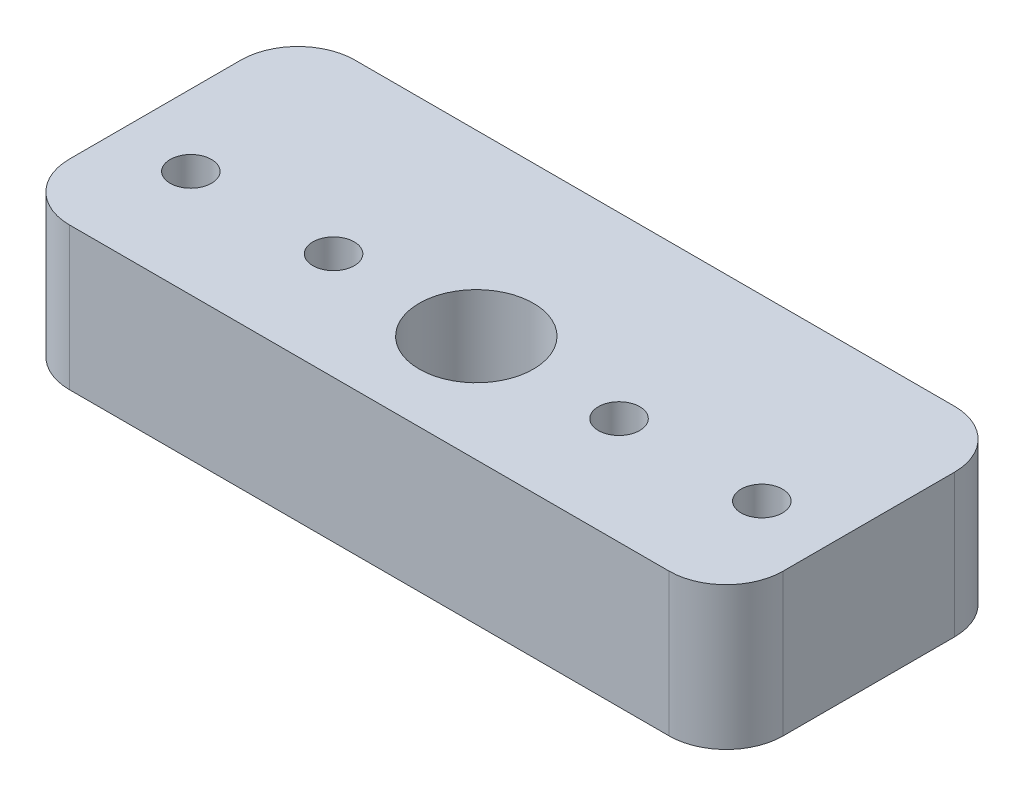
SolidWorks part; units mm, degrees
ref_plane "Front Plane" through (0, 0, 0) normal (0, 0, 1) x (1, 0, 0)
ref_plane "Top Plane" through (0, 0, 0) normal (0, 1, 0) x (1, 0, 0)
ref_plane "Right Plane" through (0, 0, 0) normal (1, 0, 0) x (0, 0, -1)
sketch "Sketch1" plane through (0, 0, 0) normal (0, 1, 0) x (1, 0, 0)
  line L0 (-25, -2.5) -> (25, -2.5) construction
  line L1 (-21, 10) -> (21, 10)
  line L2 (-25, 6) -> (-25, -6)
  line L3 (-21, -10) -> (21, -10)
  line L4 (25, 6) -> (25, -6)
  line L5 (-25, 10) -> (25, -10) construction
  line L6 (-25, -10) -> (25, 10) construction
  line L7 (0, -10) -> (0, 10) construction
  line L8 (25, 10) -> (-25, -10) construction
  arc A0 (-25, -6) -> (-21, -10) centre (-21, -6) ccw
  arc A1 (21, -10) -> (25, -6) centre (21, -6) ccw
  arc A2 (21, 10) -> (25, 6) centre (21, 6) cw
  arc A3 (-21, 10) -> (-25, 6) centre (-21, 6) ccw
  circle A4 centre (0, -2.5) radius 4
  circle A5 centre (10, -2.5) radius 1.45
  circle A6 centre (20, -2.5) radius 1.45
  circle A7 centre (-20, -2.5) radius 1.45
  circle A8 centre (-10, -2.5) radius 1.45
  point P0 (0, 0)
  dimension "D3" = 4
  dimension "D4" = 8
  dimension "D5" = 2.9
  dimension "D6" = 2.9
  dimension "D1" = 20
  dimension "D7" = 7.5
  dimension "D8" = 10
  dimension "D9" = 40
  dimension "D2" = 5
extrude "Boss-Extrude1" add sketch "Sketch1" along normal blind 10
equation "\"Y-ROD-SPACING\"=75"
equation "\"Y-BED-OFFSET\"=2"
equation "\"Y-BED-ROD-INSET\"=3.5"
equation "\"T-SLOT-NUT-FILLET-RADIUS\"=0.5"
equation "\"T-SLOT-SCREW-SHAFT-RADIUS\"=1.55"
equation "\"T-SLOT-SCREW-SHAFT-CUTOUT-LENGTH\"=11.0"
equation "\"T-SLOT-NUT-DEPTH\"=3.5"
equation "\"T-SLOT-NUT-WIDTH\"=2.85"
equation "\"T-SLOT-NUT-END-DISTANCE\"=8"
equation "\"ACRYLIC-TAB-CUTOUT-SIZE\"=\"ACRYLIC-THICKNESS\"+\"ACRYLIC-TAB-TOLERANCE\"*2"
equation "\"ACRYLIC-M3-HOLE\"=2.9"
equation "\"SMOOTHROD-CAP-SCREW-DISTANCE\"=20"
equation "\"D5@Sketch1\"=\"ACRYLIC-M3-HOLE\""
equation "\"D6@Sketch1\"=\"ACRYLIC-M3-HOLE\""
equation "\"D8@Sketch1\"=\"SMOOTHROD-CAP-SCREW-DISTANCE\"/2"
equation "\"ACRYLIC-TAB-WIDTH\"=\"ACRYLIC-THICKNESS\""
equation "\"FRAME-WIDTH-INNER\"=370"
equation "\"NEMA17-HOLE-SPACING\"=31"
equation "\"NEMA17-CENTRAL-CUTOUT\"=22.5"
equation "\"Z-BRACKET-REACH\"=55"
equation "\"TOP-BRACKET-SPACING\"=40"
equation "\"D9@Sketch1\"=\"TOP-BRACKET-SPACING\""
equation "\"D2@Sketch1\"=\"ACRYLIC-TAB-WIDTH\"/2"
equation "\"X-ROD-SPACING\"=45"
equation "\"Z-ROD-SPACING\"=17.5"
equation "\"ACRYLIC-THICKNESS\"=10"
equation "\"ACRYLIC-THICKNESS2\"=4.5"
equation "\"SMOOTHROD-X-LENGTH\"=350"
equation "\"SMOOTHROD-Y-LENGTH\"=350"
equation "\"SMOOTHROD-Z-LENGTH\"=350"
equation "\"SMOOTHROD-TIGHTENING-HEADROOM\"=.25"
equation "\"LEADSCREW-Z-LENGTH\"=300"
equation "\"SCREW-LENGTH-FRAME\"=\"ACRYLIC-THICKNESS\" + 10"
equation "\"SCREW-HEAD-RADIUS\"=6"
equation "\"PRINTED-X-SMOOTHROD-DIAMETER\"=9.0"
equation "\"PRINTED-X-SMOOTHROD-CUTOUT\"=10"
equation "\"PRINTED-X-BASE-HEIGHT\"=10"
equation "\"PRINTED-LM8UU-CUTOUT-SIZE\"=15.5"
equation "\"PRINTED-LM8UU-CUTOUT-LENGTH\"=24.5"
equation "\"PRINTED-X-IDLER-HEIGHT\"=16"
equation "\"PSU-MOUNTING-WIDTH\"=95"
equation "\"PSU-MOUNTING-HEIGHT\"=177"
equation "\"D1@Boss-Extrude1\"=\"ACRYLIC-THICKNESS\""
